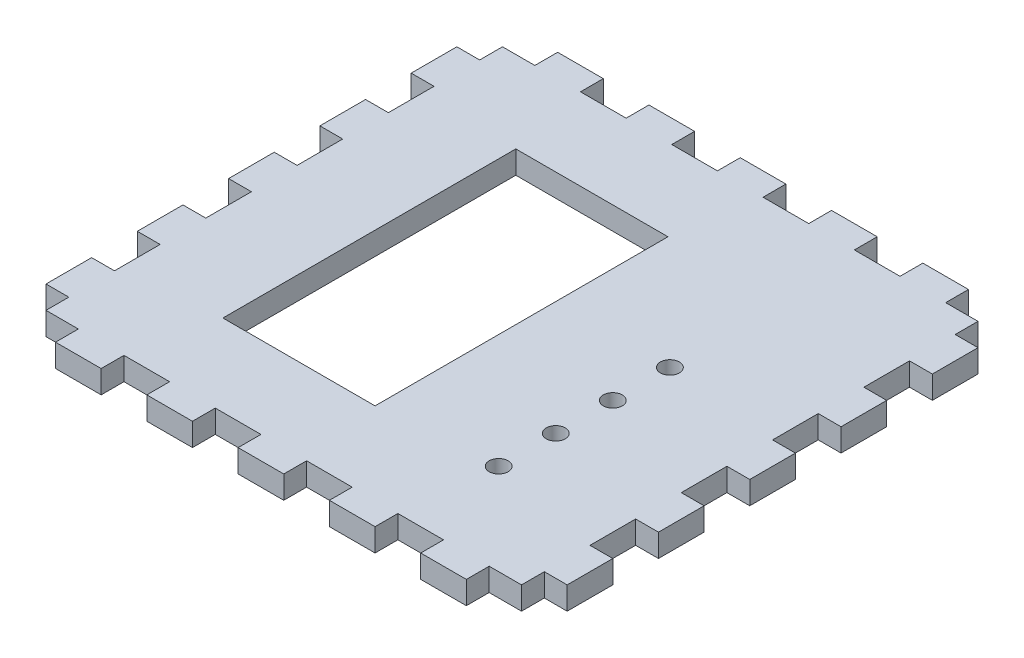
SolidWorks part; units mm, degrees
ref_plane "Front Plane" through (0, 0, 0) normal (0, 0, 1) x (1, 0, 0)
ref_plane "Top Plane" through (0, 0, 0) normal (0, 1, 0) x (1, 0, 0)
ref_plane "Right Plane" through (0, 0, 0) normal (1, 0, 0) x (0, 0, -1)
sketch "Sketch1" plane through (0, 0, 0) normal (0, 1, 0) x (1, 0, 0)
  line L0 (2.5, 38.5) -> (2.5, 60) construction
  line L1 (-62.5, -60) -> (62.5, -60)
  line L2 (-62.5, -60) -> (-62.5, 60)
  line L3 (-62.5, 60) -> (62.5, 60)
  line L4 (62.5, -60) -> (62.5, 60)
  line L5 (-62.5, -60) -> (62.5, 60) construction
  line L6 (-62.5, 60) -> (62.5, -60) construction
  line L7 (-37.5, -38.5) -> (2.5, -38.5)
  line L8 (-37.5, -38.5) -> (-37.5, 38.5)
  line L9 (-37.5, 38.5) -> (2.5, 38.5)
  line L10 (2.5, -38.5) -> (2.5, 38.5)
  line L11 (-37.5, -38.5) -> (2.5, 38.5) construction
  line L12 (-37.5, 38.5) -> (2.5, -38.5) construction
  line L13 (2.5, -38.5) -> (2.5, -60) construction
  line L14 (-37.5, 38.5) -> (-62.5, 38.5) construction
  line L15 (32.5, -36) -> (32.5, -21) construction
  line L16 (2.5, -38.5) -> (32.5, -38.5) construction
  line L17 (32.5, -21) -> (32.5, -6) construction
  line L18 (32.5, -6) -> (32.5, 9) construction
  line L19 (32.5, -38.5) -> (62.5, -38.5) construction
  line L20 (-54, 66) -> (-54, 60)
  line L21 (-62.5, 54) -> (-68.5, 54)
  line L22 (-54, 66) -> (-42, 66)
  line L23 (-42, 66) -> (-42, 60)
  line L24 (-18, 66) -> (-18, 60)
  line L25 (-30, 66) -> (-30, 60)
  line L26 (-30, 66) -> (-18, 66)
  line L27 (6, 66) -> (6, 60)
  line L28 (-6, 66) -> (-6, 60)
  line L29 (-6, 66) -> (6, 66)
  line L30 (30, 66) -> (30, 60)
  line L31 (18, 66) -> (18, 60)
  line L32 (18, 66) -> (30, 66)
  line L33 (54, 66) -> (54, 60)
  line L34 (42, 66) -> (42, 60)
  line L35 (42, 66) -> (54, 66)
  line L36 (-68.5, 54) -> (-68.5, 42)
  line L37 (-68.5, 42) -> (-62.5, 42)
  line L38 (-62.5, 30) -> (-68.5, 30)
  line L39 (-68.5, 30) -> (-68.5, 18)
  line L40 (-68.5, 18) -> (-62.5, 18)
  line L41 (-62.5, 6) -> (-68.5, 6)
  line L42 (-68.5, 6) -> (-68.5, -6)
  line L43 (-68.5, -6) -> (-62.5, -6)
  line L44 (-62.5, -18) -> (-68.5, -18)
  line L45 (-68.5, -18) -> (-68.5, -30)
  line L46 (-68.5, -30) -> (-62.5, -30)
  line L47 (-62.5, -42) -> (-68.5, -42)
  line L48 (-68.5, -42) -> (-68.5, -54)
  line L49 (-68.5, -54) -> (-62.5, -54)
  line L51 (0, -55) -> (0, 55) construction
  line L52 (68.5, -54) -> (62.5, -54)
  line L53 (68.5, -42) -> (68.5, -54)
  line L54 (62.5, -42) -> (68.5, -42)
  line L55 (68.5, -30) -> (62.5, -30)
  line L56 (68.5, -18) -> (68.5, -30)
  line L57 (62.5, -18) -> (68.5, -18)
  line L58 (68.5, -6) -> (62.5, -6)
  line L59 (68.5, 6) -> (68.5, -6)
  line L60 (62.5, 6) -> (68.5, 6)
  line L61 (68.5, 18) -> (62.5, 18)
  line L62 (68.5, 30) -> (68.5, 18)
  line L63 (62.5, 30) -> (68.5, 30)
  line L64 (68.5, 42) -> (62.5, 42)
  line L65 (68.5, 54) -> (68.5, 42)
  line L66 (-55, 0) -> (55, 0) construction
  line L67 (42, -66) -> (54, -66)
  line L68 (42, -66) -> (42, -60)
  line L69 (54, -66) -> (54, -60)
  line L70 (18, -66) -> (30, -66)
  line L71 (18, -66) -> (18, -60)
  line L72 (30, -66) -> (30, -60)
  line L73 (-6, -66) -> (6, -66)
  line L74 (-6, -66) -> (-6, -60)
  line L75 (6, -66) -> (6, -60)
  line L76 (-30, -66) -> (-18, -66)
  line L77 (-30, -66) -> (-30, -60)
  line L78 (-18, -66) -> (-18, -60)
  line L79 (-42, -66) -> (-42, -60)
  line L80 (-54, -66) -> (-42, -66)
  line L81 (-54, -66) -> (-54, -60)
  line L82 (62.5, 54) -> (68.5, 54)
  circle A0 centre (32.5, 9) radius 2.5
  circle A1 centre (32.5, -6) radius 2.5
  circle A2 centre (32.5, -21) radius 2.5
  circle A3 centre (32.5, -36) radius 2.5
  point P0 (0, 0)
  point P6 (-17.5, 0)
  dimension "D7" = 6
  dimension "D8" = 12
  dimension "D1" = 125
  dimension "D2" = 5
  dimension "D4" = 40
  dimension "D5" = 25
  dimension "D10" = 8.5
  dimension "D12" = 12
  dimension "D13" = 6
  dimension "D14" = 6
  dimension "D11" = 5
extrude "Boss-Extrude2" add sketch "Sketch1" along normal blind 6 contours L1 L4 L3 L2 A3 A2 A1 | L39 L40 L2 L38 | L36 L37 L2 L21 | L45 L46 L2 L44 | L42 L43 L2 L41 | L48 L49 L2 L47 | L81 L80 L79 L1 | L76 L78 L1 L77 | L73 L75 L1 L74 | L70 L72 L1 L71 | L67 L69 L1 L68 | L54 L4 L52 L53 | L57 L4 L55 L56 | L60 L4 L58 L59 | L63 L4 L61 L62 | L82 L4 L64 L65 | L35 L34 L3 L33 | L32 L31 L3 L30 | L29 L28 L3 L27 | L23 L22 L20 L3 | L26 L25 L3 L24 region at (4.3362, 0, -0.0895) region at (-48, 0, 63) region at (-65.5, 0, 48) region at (-24, 0, 63) region at (-65.5, 0, 24) region at (0, 0, 63) region at (-65.5, 0, 0) region at (24, 0, 63) region at (-65.5, 0, -24) region at (48, 0, 63) region at (-65.5, 0, -48) region at (65.5, 0, 48) region at (-48, 0, -63) region at (65.5, 0, 24) region at (-24, 0, -63) region at (65.5, 0, 0) region at (0, 0, -63) region at (65.5, 0, -24) region at (24, 0, -63) region at (65.5, 0, -48) region at (48, 0, -63)
sketch "Sketch2" plane through (0, 6, 0) normal (0, 1, 0) x (1, 0, 0)
  text T0 "Trappen \r\n        maar!" font "Century Gothic" height 3.5
